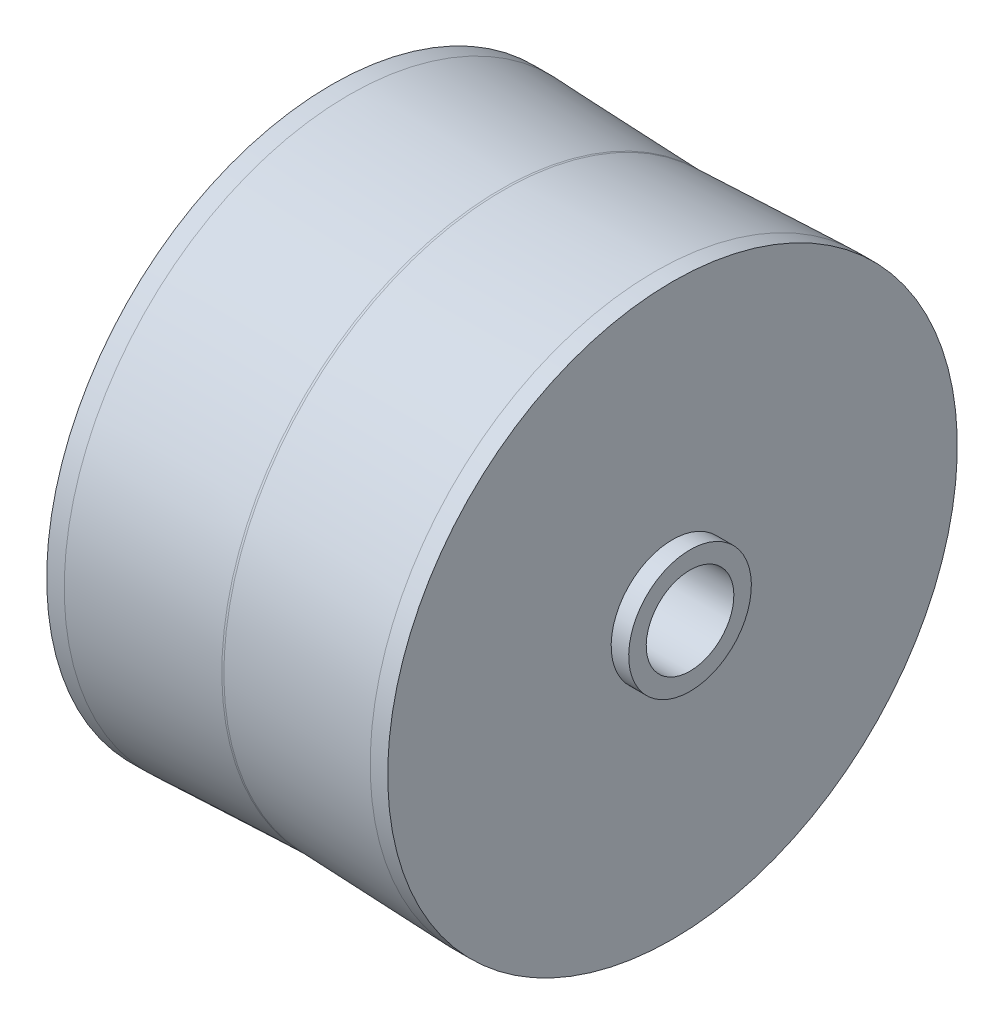
SolidWorks part; units mm, degrees
ref_plane "XY" through (0, 0, 0) normal (0, 0, 1) x (1, 0, 0)
ref_plane "XZ" through (0, 0, 0) normal (0, 1, 0) x (1, 0, 0)
ref_plane "YZ" through (0, 0, 0) normal (1, 0, 0) x (0, 0, -1)
ref_axis "X" through (-29.15, 0, 0) along (1, 0, 0)
ref_axis "Y" through (0, -41.91, 0) along (0, 1, 0)
ref_axis "Z" through (0, 0, 41.91) along (0, 0, -1)
sketch "Sketch1" plane through (0, 0, 0) normal (0, 0, 1) x (1, 0, 0)
  line L0 (-27.25, 0) -> (27.25, 0) construction
  line L1 (-27.25, 6.35) -> (27.25, 6.35)
  line L2 (27.25, 6.35) -> (27.25, 8.89)
  line L3 (27.25, 8.89) -> (24.71, 8.89)
  line L4 (24.71, 8.89) -> (24.71, 41.275)
  line L6 (-24.71, 41.275) -> (-24.71, 8.89)
  line L7 (-24.71, 8.89) -> (-27.25, 8.89)
  line L8 (-27.25, 8.89) -> (-27.25, 6.35)
  line L9 (0, 6.35) -> (0, 0) construction
  line L10 (-22.17, 41.275) -> (-0.1492, 40.4528)
  line L11 (0.1492, 40.4528) -> (22.17, 41.275)
  line L12 (22.17, 41.275) -> (24.71, 41.275)
  line L13 (0, 44.45) -> (0, 6.35) construction
  line L14 (-22.17, 41.275) -> (-24.71, 41.275)
  arc A0 (-0.1492, 40.4528) -> (0.1492, 40.4528) centre (0, 44.45) ccw
  point P4 (0, 0)
  point P13 (25.98, 8.89)
  dimension "D6" = 4
  dimension "D7" = 38.1
  dimension "D1" = 54.5
  dimension "D2" = 12.7
  dimension "D3" = 41.275
  dimension "D4" = 17.78
  dimension "D5" = 2.54
  dimension "D8" = 2.54
revolve "Revolve1" add sketch "Sketch1" angle 360 about L0
